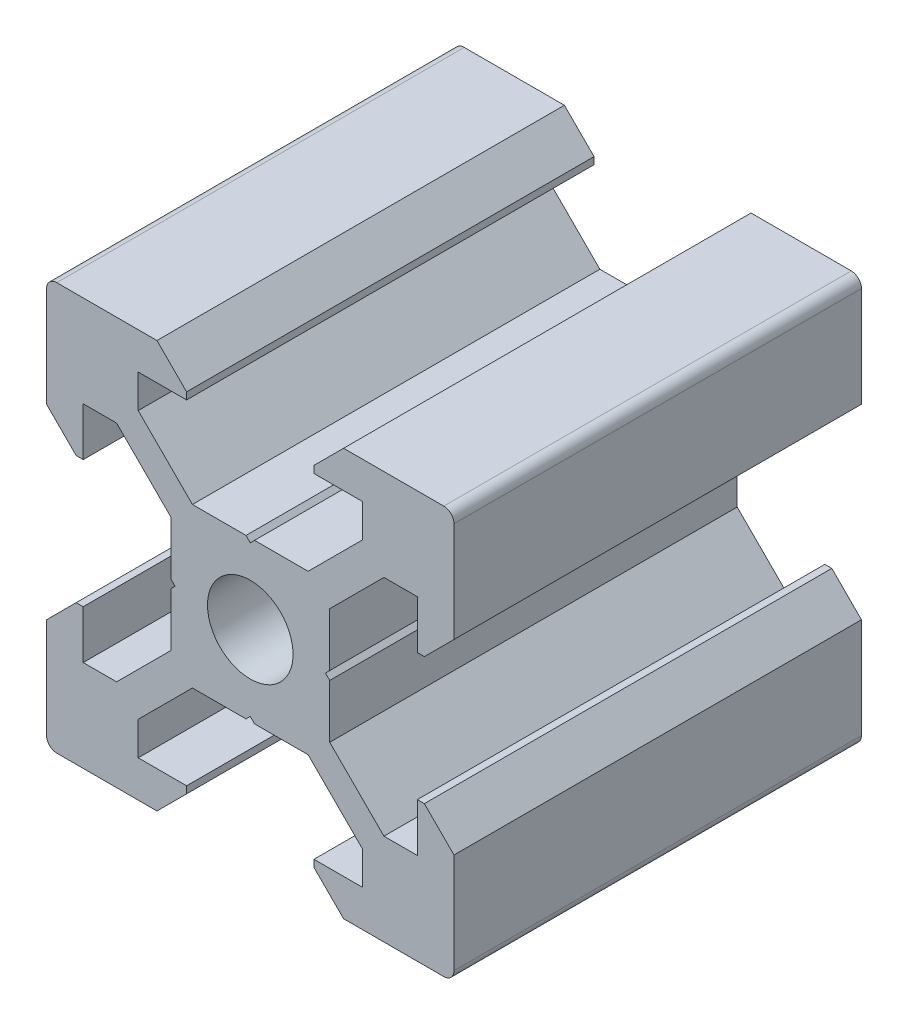
SolidWorks part; units mm, degrees
ref_plane "Plan de face" through (0, 0, 0) normal (0, 0, 1) x (1, 0, 0)
ref_plane "Plan de dessus" through (0, 0, 0) normal (0, 1, 0) x (1, 0, 0)
ref_plane "Plan de droite" through (0, 0, 0) normal (1, 0, 0) x (0, 0, -1)
ref_axis "Axe" through (0, 0, -13.782) along (0, 0, 1)
sketch "Esquisse1" plane through (0, 0, 0) normal (0, 0, 1) x (1, 0, 0)
  line L0 (0, 22.8977) -> (0, -22.8977) construction
  line L1 (-33.6074, 0) -> (33.6074, 0) construction
  line L2 (0, 0) -> (-22.2114, 22.2114) construction
  line L3 (-9.5, 10) -> (-4.58, 10)
  line L4 (-4.58, 10) -> (-3.125, 8.545)
  line L5 (-3.125, 8.545) -> (-3.125, 8.2)
  line L6 (-3.125, 8.2) -> (-5.5, 8.2)
  line L7 (-2.8393, 3.9) -> (-5.5, 6.5607)
  line L8 (-2.8393, 3.9) -> (-0.21, 3.9)
  line L9 (-5.5, 6.5607) -> (-5.5, 8.2)
  line L10 (0, 3.69) -> (0, 2.1)
  line L11 (-3.9, 2.8393) -> (-6.5607, 5.5)
  line L12 (-8.545, 3.125) -> (-8.2, 3.125)
  line L13 (-8.2, 3.125) -> (-8.2, 5.5)
  line L14 (-6.5607, 5.5) -> (-8.2, 5.5)
  line L15 (-10, 4.58) -> (-8.545, 3.125)
  line L16 (-10, 9.5) -> (-10, 4.58)
  line L17 (-0.21, 3.9) -> (0, 3.69)
  line L18 (-3.9, 2.8393) -> (-3.9, 0.21)
  line L19 (-3.69, 0) -> (-2.1, 0)
  line L20 (-3.9, 0.21) -> (-3.69, 0)
  arc A0 (-2.1, 0) -> (0, 2.1) centre (0, 0) cw
  arc A1 (-9.5, 10) -> (-10, 9.5) centre (-9.5, 9.5) ccw
  point P4 (0, 0)
  point P7 (0, 0)
  point P30 (-10, 10)
  dimension "D5" = 11
  dimension "D2" = 2.1
  dimension "D3" = 6.25
  dimension "D10" = 0.5
  dimension "D4" = 9.16
  dimension "D6" = 1.5
  dimension "D7" = 1.8
  dimension "D8" = 4.3
  dimension "D9" = 20
  dimension "D11" = 0.42
extrude "Boss.-Extru.1" add sketch "Esquisse1" along normal blind 20
sketch "Esquisse3" plane through (0, 0, 20) normal (0, 0, 1) x (1, 0, 0)
  line L0 (0, 0) -> (-9.8536, 9.8536) construction
  line L1 (-8.2, 8.2) -> (-8.2, 6.57)
  line L2 (-8.2, 6.57) -> (-7.54, 6.57)
  line L3 (-7.54, 6.57) -> (-6.57, 7.54)
  line L4 (-8.2, 3.125) -> (-8.2, 5.5) construction
  line L5 (-6.57, 8.2) -> (-6.57, 7.54)
  line L6 (-8.2, 8.2) -> (-6.57, 8.2)
  line L7 (-5.5, 6.5607) -> (-5.5, 8.2) construction
  arc A0 (-9.5, 10) -> (-10, 9.5) centre (-9.5, 9.5) ccw construction
  point P13 (-7.055, 7.055)
  point P14 (-6.57, 7.87)
  dimension "D1" = 1.07
extrude "Enlèv. mat.-Extru.1" [suppressed] cut sketch "Esquisse3" against normal through all
pattern_circular "Répétition circulaire1" count 4 every 90 about axis through (0, 0, -13.782) along (0, 0, 1) of "Boss.-Extru.1", "Enlèv. mat.-Extru.1"
